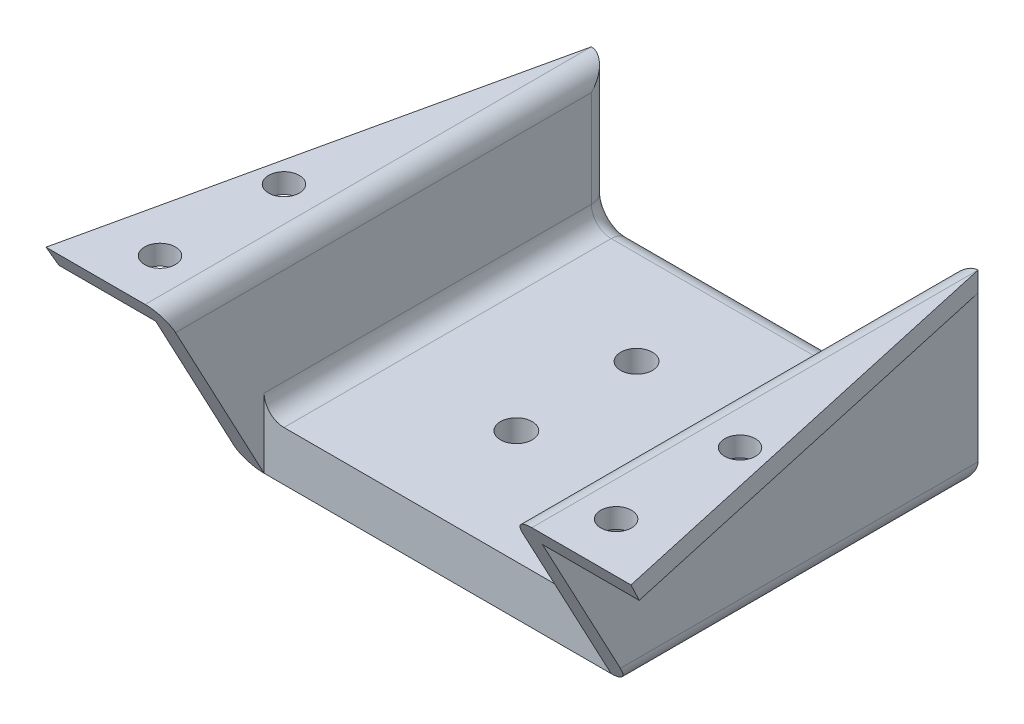
SolidWorks part; units mm, degrees
ref_plane "Front Plane" through (0, 0, 0) normal (0, 0, 1) x (1, 0, 0)
ref_plane "Top Plane" through (0, 0, 0) normal (0, 1, 0) x (1, 0, 0)
ref_plane "Right Plane" through (0, 0, 0) normal (1, 0, 0) x (0, 0, -1)
sketch "Sketch2" plane through (0, 0, 0) normal (0, 1, 0) x (1, 0, 0)
  line L1 (-17.5, -17.5) -> (17.5, -17.5)
  line L2 (-17.5, -17.5) -> (-17.5, 17.5)
  line L3 (-17.5, 17.5) -> (17.5, 17.5)
  line L4 (17.5, -17.5) -> (17.5, 17.5)
  line L5 (-17.5, -17.5) -> (17.5, 17.5) construction
  line L6 (-17.5, 17.5) -> (17.5, -17.5) construction
  circle A0 centre (0, 0) radius 7 construction
  circle A1 centre (7, 0) radius 1.6
  circle A2 centre (-3.5, -6.0622) radius 1.6
  circle A3 centre (-3.5, 6.0622) radius 1.6
  point P0 (0, 0)
  point P16 (0, 0)
  dimension "D1" = 14
  dimension "D2" = 3.2
  dimension "D4" = 35
  dimension "D5" = 35
  dimension "D3" = 3
extrude "Boss-Extrude1" add sketch "Sketch2" along normal blind 5
sketch "Sketch3" plane through (17.5, 0, 0) normal (1, 0, 0) x (0, 0, -1)
  line L0 (-17.5, 0) -> (-27.5, 18.75)
  line L1 (-27.5, 18.75) -> (17.5, 18.75)
  line L3 (-17.5, 0) -> (17.5, 0)
  line L4 (17.5, 18.75) -> (17.5, 0)
  dimension "D1" = 18.75
  dimension "D2" = 45
extrude "Boss-Extrude2" add sketch "Sketch3" along normal blind 2
mirror "Mirror1" about plane through (0, 0, 0) normal (1, 0, 0) of "Boss-Extrude2"
sketch "Sketch4" plane through (0, 18.75, 0) normal (0, 1, 0) x (1, 0, 0)
  line L0 (-19.5, -27.5) -> (-29.5, -27.5)
  line L1 (-29.5, -27.5) -> (-19.5, 17.5)
  line L3 (-19.5, 17.5) -> (-19.5, -27.5) construction
  line L4 (-19.5, 17.5) -> (-19.5, -27.5)
  line L6 (-23, -10) -> (-23, -22.5) construction
  circle A0 centre (-23, -22.5) radius 1.55
  circle A1 centre (-23, -10) radius 1.55
  dimension "D2" = 3.1
  dimension "D3" = 3.1
  dimension "D1" = 10
  dimension "D4" = 12.5
  dimension "D6" = 5
  dimension "D7" = 3.5
extrude "Boss-Extrude3" add sketch "Sketch4" against normal blind 2
sketch "Sketch5" plane through (-19.5, 0, 0) normal (1, 0, 0) x (0, 0, -1)
  line L0 (-27.5, 18.75) -> (-26.4333, 16.75)
  line L1 (-26.4333, 16.75) -> (-27.5, 16.75)
  line L2 (-27.5, 16.75) -> (-27.5, 18.75)
extrude "Cut-Extrude1" cut sketch "Sketch5" against normal through all
mirror "Mirror2" about plane through (0, 0, 0) normal (1, 0, 0) of "Cut-Extrude1", "Boss-Extrude3"
fillet "Fillet1" radius 2 10 edges at (17.5, 11.875, -17.5) (-17.5, 11.875, -17.5) (-17.5, 18.75, 5) (17.5, 18.75, 5) (0, 5, -17.5) (0, 0, -17.5) (17.5, 5, 0) (-17.5, 5, 0) (-19.5, 0, 0) (19.5, 0, 0)
